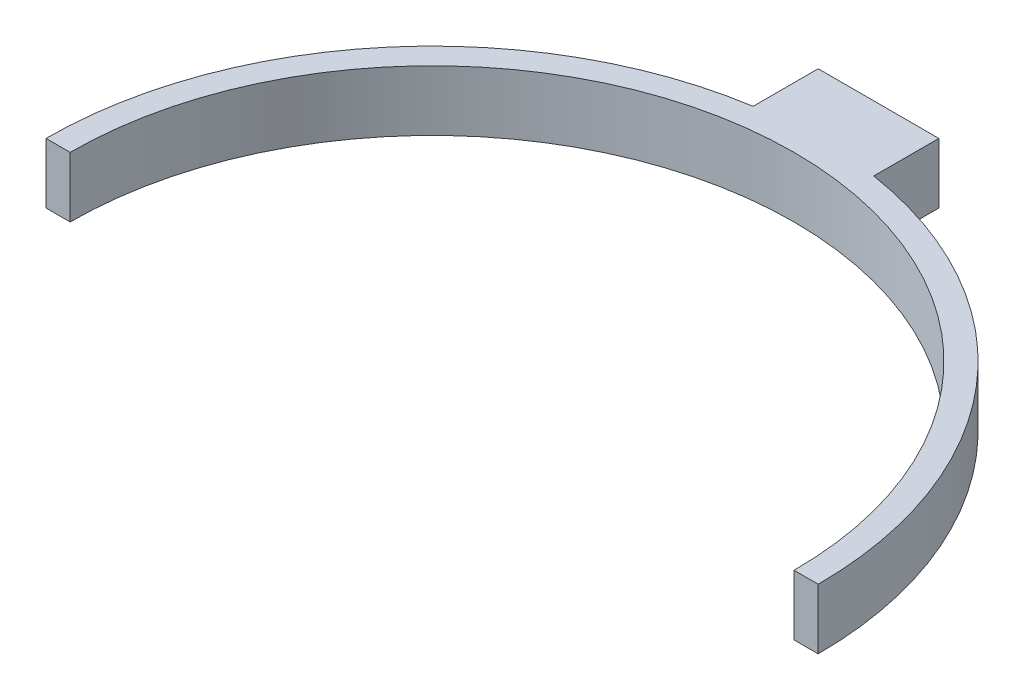
SolidWorks part; units mm, degrees
ref_plane "前视基准面" through (0, 0, 0) normal (0, 0, 1) x (1, 0, 0)
ref_plane "上视基准面" through (0, 0, 0) normal (0, 1, 0) x (1, 0, 0)
ref_plane "右视基准面" through (0, 0, 0) normal (1, 0, 0) x (0, 0, -1)
sketch "草图1" plane through (0, 0, 0) normal (0, 1, 0) x (1, 0, 0)
  line L0 (-32, 0) -> (-30, 0)
  line L1 (30, 0) -> (32, 0)
  arc A0 (30, 0) -> (-30, 0) centre (0, 0) ccw
  arc A1 (32, 0) -> (-32, 0) centre (0, 0) ccw
extrude "凸台-拉伸1" add sketch "草图1" along normal blind 5
sketch "草图2" plane through (0, 0, 0) normal (0, 1, 0) x (1, 0, 0)
  line L0 (0, 32) -> (0, 37)
  line L1 (0, 37) -> (5, 37)
  line L2 (5, 37) -> (5, 30.4653)
  line L3 (5, 30.4653) -> (-5, 30.4653)
  line L4 (-5, 30.4653) -> (-5, 37)
  line L5 (-5, 37) -> (0, 37)
  arc A0 (32, 0) -> (-32, 0) centre (0, 0) ccw construction
extrude "凸台-拉伸2" add sketch "草图2" along normal blind 5 contours L5 L4 L3 L2 L1 region at (2.5, 0, -36.8805)
